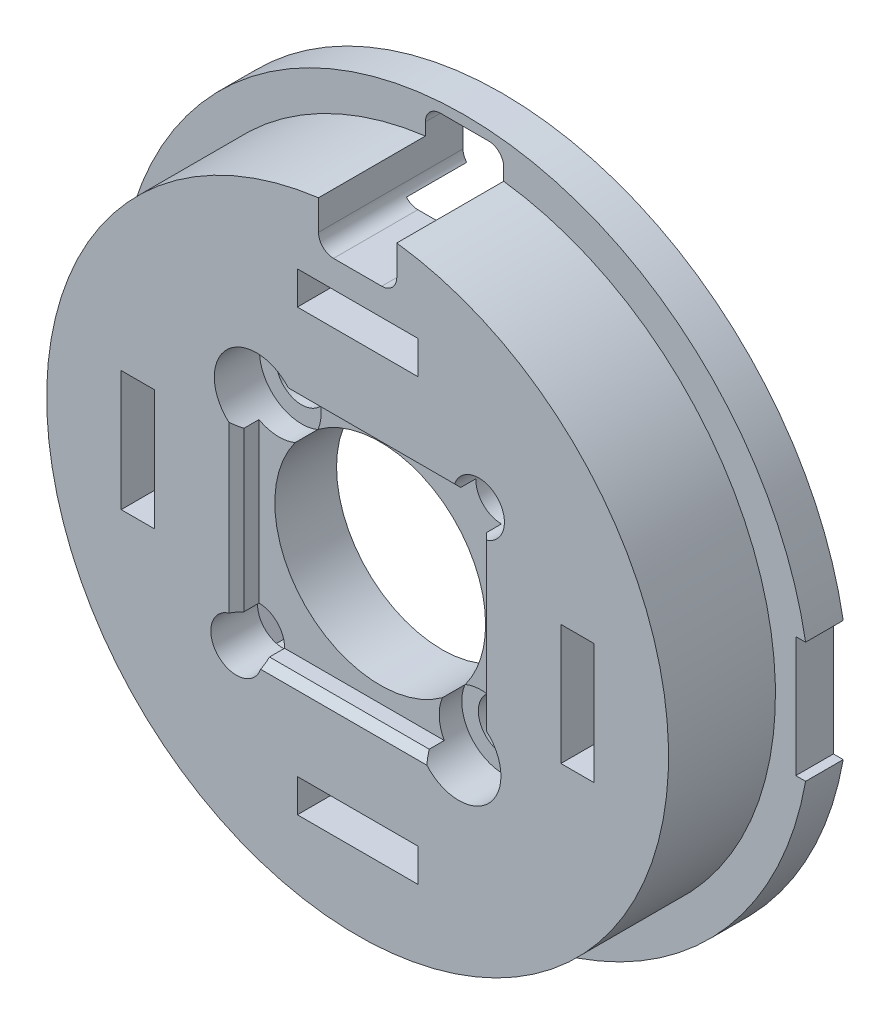
SolidWorks part; units mm, degrees
other "标注1"
sketch "草图10" plane through (17.4, 17.4, 7.6) normal (0.4476, 0.4282, 0.7851) x (0.8625, 0.025, -0.5054)
ref_plane "前视基准面" through (0, 0, 0) normal (0, 0, 1) x (1, 0, 0)
ref_plane "上视基准面" through (0, 0, 0) normal (0, 1, 0) x (1, 0, 0)
ref_plane "右视基准面" through (0, 0, 0) normal (1, 0, 0) x (0, 0, -1)
other "Configuration Table"
sketch "草图1" plane through (0, 0, 0) normal (0, 0, 1) x (1, 0, 0)
  circle A0 centre (0, 0) radius 17.4
  dimension "D1" = 34.8
extrude "凸台-拉伸1" add sketch "草图1" along normal blind 5.6
sketch "草图2" plane through (0, 0, 5.6) normal (0, 0, 1) x (1, 0, 0)
  line L0 (5.5154, -5.5154) -> (6.7175, -6.7175) construction
  line L1 (-6.7175, 6.7175) -> (-5.0175, 6.7175)
  line L2 (-6.7175, 6.7175) -> (-6.7175, 5.0175)
  line L3 (5.0175, -6.7175) -> (6.7175, -6.7175)
  line L4 (6.7175, -5.0175) -> (6.7175, -6.7175)
  line L5 (-6.7175, 6.7175) -> (-0.0325, 0.0325) construction
  line L6 (-6.7175, 6.7175) -> (6.7175, -6.7175)
  circle A0 centre (-6.7175, 6.7175) radius 1.7
  circle A2 centre (6.7175, -6.7175) radius 1.7
  arc A4 (-5.5154, -5.5154) -> (-6.7175, -5.0175) centre (-6.7175, -6.7175) ccw [skipped]
  arc A5 (5.0175, 6.7175) -> (5.5154, 5.5154) centre (6.7175, 6.7175) ccw [skipped]
  point P0 (0, 0)
  point P16 (0, 0)
  dimension "D3" = 3.4
  dimension "D1" = 19
  dimension "D2" = 9.5
  dimension "D4" = 4
extrude "切除-拉伸1" cut sketch "草图2" against normal through all contours A0 | A2
sketch "草图3" plane through (0, 0, 5.6) normal (0, 0, 1) x (1, 0, 0)
  circle A0 centre (0, 0) radius 7
  dimension "D1" = 14
extrude "切除-拉伸2" cut sketch "草图3" against normal through all
sketch "草图4" plane through (0, 0, 5.6) normal (0, 0, 1) x (1, 0, 0)
  circle A1 centre (-6.7175, 6.7175) radius 2.8
  circle A2 centre (6.7175, -6.7175) radius 2.8
  dimension "D1" = 5.6
  dimension "D2" = 5.6
extrude "切除-拉伸3" cut sketch "草图4" against normal blind 3
sketch "草图5" plane through (0, 0, 5.6) normal (0, 0, 1) x (1, 0, 0)
  line L1 (-8.05, 8) -> (8.05, 8)
  line L2 (-8.05, 8) -> (-8.05, -8)
  line L3 (-8.05, -8) -> (8.05, -8)
  line L4 (8.05, 8) -> (8.05, -8)
  line L5 (-8.05, 8) -> (8.05, -8) construction
  line L6 (-8.05, -8) -> (8.05, 8) construction
  circle A0 centre (8.05, 8) radius 1.7
  circle A1 centre (-8.05, -8) radius 1.7
  point P0 (0, 0)
  dimension "D3" = 3.4
  dimension "D4" = 3.4
  dimension "D1" = 16.1
  dimension "D2" = 16
extrude "切除-拉伸4" cut sketch "草图5" against normal through all contours A1 | A0
sketch "草图6" plane through (0, 0, 0) normal (0, 0, -1) x (-1, 0, 0)
  line L0 (4.7668, -8) -> (6.4084, -10.8433)
  line L1 (-4.7668, 8) -> (-6.4084, 10.8433)
  line L2 (-6.4084, 10.8433) -> (-9.6916, 10.8433)
  line L3 (-9.6916, 10.8433) -> (-11.3332, 8)
  line L4 (-11.3332, 8) -> (-9.6916, 5.1567)
  line L5 (-9.6916, 5.1567) -> (-6.4084, 5.1567)
  line L6 (-6.4084, 5.1567) -> (-4.7668, 8)
  line L7 (6.4084, -10.8433) -> (9.6916, -10.8433)
  line L8 (9.6916, -10.8433) -> (11.3332, -8)
  line L9 (11.3332, -8) -> (9.6916, -5.1567)
  line L10 (9.6916, -5.1567) -> (6.4084, -5.1567)
  line L11 (6.4084, -5.1567) -> (4.7668, -8)
  circle A0 centre (-8.05, 8) radius 2.8433 construction
  point P17 (0, 0)
  dimension "D1" = 2
extrude "切除-拉伸5" cut sketch "草图6" against normal blind 2.5
sketch "草图7" plane through (0, 0, 5.6) normal (0, 0, 1) x (1, 0, 0)
  line L5 (-8.05, 8.05) -> (8.05, 8.05)
  line L6 (-8.05, 8.05) -> (-8.05, -8.05)
  line L11 (-8.05, -8.05) -> (8.05, -8.05)
  line L12 (8.05, 8.05) -> (8.05, -8.05)
  line L13 (-8.05, 8.05) -> (8.05, -8.05) construction
  line L14 (-8.05, -8.05) -> (8.05, 8.05) construction
  point P0 (0, 0)
  dimension "D1" = 16.1
  dimension "D2" = 16.1
extrude "切除-拉伸6" cut sketch "草图7" against normal blind 1.5
chamfer "倒角1" distance 0.5 angle 45 4 edges at (1.0479, 8.05, 5.6) (8.05, 1.0226, 5.6) (-1.0479, -8.05, 5.6) (-8.05, -1.0226, 5.6)
sketch "草图8" plane through (0, 0, 0) normal (1, 0, 0) x (0, 0, -1)
  line L0 (0, 17.4) -> (0, 17.2)
  line L1 (0, 17.4) -> (0.2, 17.4)
  line L2 (0.2, 17.4) -> (0, 17.2)
  dimension "D1" = 0.2
  dimension "D2" = 0.2
ref_axis "基准轴1" through (0, 0, 0) along (0, 0, 1)
revolve "旋转1" add sketch "草图8" angle 360 about axis through (0, 0, 0) along (0, 0, 1)
sketch "草图9" plane through (0, 0, 5.6) normal (0, 0, 1) x (1, 0, 0)
  line L0 (0, 0) -> (15, 0) construction
  line L1 (4, -13.5) -> (-4, -13.5)
  line L2 (13.5, 4) -> (16.5, 4)
  line L3 (13.5, 4) -> (13.5, -4)
  line L4 (13.5, -4) -> (16.5, -4)
  line L5 (16.5, 4) -> (16.5, -4)
  line L6 (13.5, 4) -> (16.5, -4) construction
  line L7 (13.5, -4) -> (16.5, 4) construction
  line L8 (4, -13.5) -> (4, -16.5)
  line L9 (4, -16.5) -> (-4, -16.5)
  line L10 (-4, -13.5) -> (-4, -16.5)
  line L11 (-13.5, -4) -> (-13.5, 4)
  line L12 (-13.5, -4) -> (-16.5, -4)
  line L13 (-16.5, -4) -> (-16.5, 4)
  line L14 (-13.5, 4) -> (-16.5, 4)
  line L15 (-4, 13.5) -> (4, 13.5)
  line L16 (-4, 13.5) -> (-4, 16.5)
  line L17 (-4, 16.5) -> (4, 16.5)
  line L18 (4, 13.5) -> (4, 16.5)
  line L19 (15.7, 4) -> (15.7, -4)
  line L20 (4, -15.7) -> (-4, -15.7)
  line L21 (-15.7, -4) -> (-15.7, 4)
  line L22 (-4, 15.7) -> (4, 15.7)
  point P22 (0, 0)
  point P31 (0, 0)
  dimension "D1" = 15
  dimension "D2" = 3
  dimension "D3" = 8
  dimension "D5" = 0.8
  dimension "D4" = 4
  dimension "D6" = 4
extrude "切除-拉伸7" cut sketch "草图9" against normal through all contours L19 L2 L3 L4 | L22 L16 L15 L18 | L21 L12 L11 L14 | L20 L8 L1 L10 region at (0, -14.6, 5.6) region at (14.6, 0, 5.6) region at (-14.6, 0, 5.6) region at (0, 14.6, 5.6)
sketch "Sketch1" plane through (0, 0, 0) normal (0, 0, 1) x (1, 0, 0)
  circle A0 centre (0, 0) radius 17.4
  circle A1 centre (0, 0) radius 20.65
  dimension "D1" = 41.3
extrude "Boss-Extrude1" add sketch "Sketch1" along normal up to surface (5.6 mm away) and the other way blind 4 up to face at (0, 0, 5.6)
sketch "Sketch2" plane through (0, 0, -4) normal (0, 0, -1) x (-1, 0, 0)
  line L0 (0, 0) -> (-17.5, 0)
  line L1 (-17.5, 0) -> (-17.5, 4)
  line L2 (-17.5, 4) -> (-20, 4)
  line L3 (-20, 4) -> (-20, -4)
  line L4 (-20, -4) -> (-17.5, -4)
  line L5 (-17.5, -4) -> (-17.5, 0)
  dimension "D1" = 2.5
  dimension "D2" = 4
  dimension "D3" = 4
  dimension "D4" = 17.5
sketch "Sketch3" plane through (0, 0, -4) normal (0, 0, -1) x (-1, 0, 0)
  circle A0 centre (0, 0) radius 20.65
  circle A1 centre (0, 0) radius 23
  circle M10 centre (0, 0) radius 20.65
  dimension "D1" = 46
extrude "Boss-Extrude2" add sketch "Sketch3" against normal blind 2.5 contours A1 M10 region at (22.3495, 0, -4)
sketch "Sketch4" plane through (0, 0, -4) normal (0, 0, -1) x (-1, 0, 0)
  circle A0 centre (0, 0) radius 18
  dimension "D1" = 36
extrude "Cut-Extrude3" cut sketch "Sketch4" against normal up to surface (4 mm away) up to face at (0, 14.6, 0)
sketch "Sketch5" plane through (0, 0, -4) normal (0, 0, -1) x (-1, 0, 0)
  line L13 (0, 0) -> (23, 0)
  line L14 (0, 0) -> (-23, 0)
  line L15 (23, -4) -> (22, -4)
  line L16 (23, -4) -> (23, 4)
  line L17 (23, 4) -> (22, 4)
  line L18 (22, -4) -> (22, 4)
  line L19 (-23, 4) -> (-22, 4)
  line L20 (-23, 4) -> (-23, -4)
  line L21 (-23, -4) -> (-22, -4)
  line L22 (-22, 4) -> (-22, -4)
  circle A0 centre (0, 0) radius 23 construction
  point P9 (0, 22)
  point P19 (0, -22)
  point P23 (0, 0)
  point P34 (0, 0)
  dimension "D4" = 8
  dimension "D5" = 1
  dimension "D6" = 4
  dimension "D3" = 2
  dimension "D7" = 2
extrude "Cut-Extrude4" cut sketch "Sketch5" against normal blind 10 contours L19 L22 L21 L20 | L16 L15 L18 L17
sketch "Sketch7" plane through (0, 0, -4) normal (0, 0, -1) x (-1, 0, 0)
  line L1 (0, 22.3) -> (2.6, 22.3)
  line L2 (0, 17.5) -> (-2.6, 17.5)
  line L3 (0, 17.5) -> (0, 22.3)
  line L4 (0, 22.3) -> (-2.6, 22.3)
  line L5 (-2.6, 17.5) -> (-2.6, 22.3)
  line L7 (0, 22.3) -> (0, 17.5)
  line L10 (0, 22.3) -> (0, 17.5)
  line L11 (0, 17.5) -> (2.6, 17.5)
  line L12 (2.6, 22.3) -> (2.6, 17.5)
  circle M5 centre (0, 0) radius 18
  dimension "D1" = 2.6
  dimension "D2" = 2.6
  dimension "D3" = 4.8
extrude "Cut-Extrude6" cut sketch "Sketch7" against normal blind 10 contours L5 L3 L4 M5 | L5 L2 L3 M5 | L12 L1 L3 M5 | L12 L3 L11 M5 region at (-1.3094, 20.1182, -4) region at (1.3094, 20.1182, -4) region at (-1.2066, 17.7222, -4) region at (1.2066, 17.7222, -4)
fillet "Fillet3" radius 1 4 edges at (2.6, 22.3, -2.75) (-2.6, 22.3, -2.75) (-2.6, 17.5, 2.8) (2.6, 17.5, 2.8)
